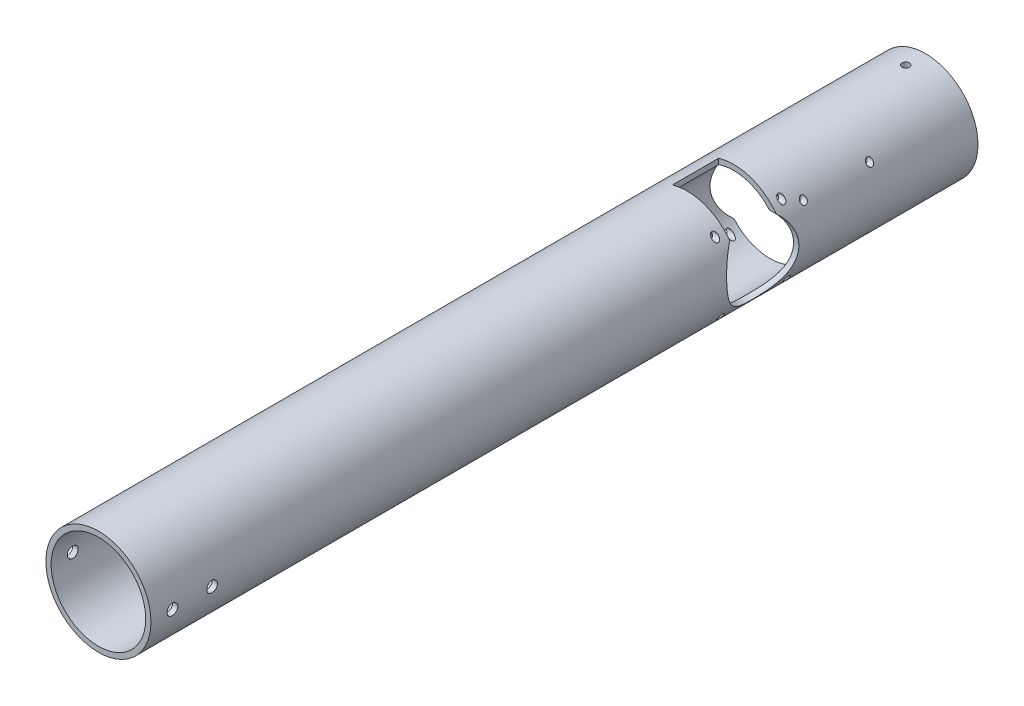
SolidWorks part; units mm, degrees
ref_plane "Front Plane" through (0, 0, 0) normal (0, 0, 1) x (1, 0, 0)
ref_plane "Top Plane" through (0, 0, 0) normal (0, 1, 0) x (1, 0, 0)
ref_plane "Right Plane" through (0, 0, 0) normal (1, 0, 0) x (0, 0, -1)
sketch "Sketch1" plane through (0, 0, 0) normal (0, 0, 1) x (1, 0, 0)
  circle A0 centre (0, 0) radius 31.75
  circle A1 centre (0, 0) radius 28.575
  dimension "D1" = 63.5
  dimension "D2" = 57.15
extrude "Boss-Extrude1" add sketch "Sketch1" along normal blind 250 and the other way blind 250 contours A1 | A0 region at (0, 0, 0)
sketch "Sketch2" plane through (0, 0, 0) normal (1, 0, 0) x (0, 0, -1)
  circle A2 centre (170, -2) radius 21.75
  dimension "D1" = 43.5
  dimension "D2" = 170
  dimension "D3" = 2
extrude "Cut-Extrude1" cut sketch "Sketch2" against normal through all
sketch "Sketch3" plane through (0, 0, 0) normal (1, 0, 0) x (0, 0, -1)
  circle A1 centre (120, 2) radius 21.75
  dimension "D1" = 120
  dimension "D2" = 43.5
  dimension "D3" = 2
extrude "Cut-Extrude2" cut sketch "Sketch3" along normal through all
sketch "Sketch5" plane through (0, 0, 0) normal (1, 0, 0) x (0, 0, -1)
  line L1 (184, -12.75) -> (156, -12.75)
  line L2 (184, -12.75) -> (184, -34.75)
  line L3 (184, -34.75) -> (156, -34.75)
  line L4 (156, -12.75) -> (156, -34.75)
  line L5 (184, -12.75) -> (156, -34.75) construction
  line L6 (184, -34.75) -> (156, -12.75) construction
  circle A0 centre (170, -2) radius 21.75 construction
  circle A1 centre (170, -2) radius 21.75 construction
  point P0 (170, -23.75)
  dimension "D1" = 28
  dimension "D2" = 22
  dimension "D3" = 170
extrude "Cut-Extrude4" cut sketch "Sketch5" against normal through all from offset 9
sketch "Sketch6" plane through (0, 0, 0) normal (1, 0, 0) x (0, 0, -1)
  line L1 (106, 34.75) -> (134, 34.75)
  line L2 (106, 34.75) -> (106, 12.75)
  line L3 (106, 12.75) -> (134, 12.75)
  line L4 (134, 34.75) -> (134, 12.75)
  line L5 (106, 34.75) -> (134, 12.75) construction
  line L6 (106, 12.75) -> (134, 34.75) construction
  circle A0 centre (120, 2) radius 21.75 construction
  circle A1 centre (120, 2) radius 21.75 construction
  point P0 (120, 23.75)
  dimension "D1" = 28
  dimension "D2" = 22
  dimension "D3" = 120
extrude "Cut-Extrude5" cut sketch "Sketch6" along normal through all from offset 9 offset against normal yes
sketch "Sketch10" plane through (0, 0, 0) normal (1, 0, 0) x (0, 0, -1)
  line L1 (210, 38) -> (130, 38)
  line L2 (210, 38) -> (210, -42)
  line L3 (210, -42) -> (130, -42)
  line L4 (130, 38) -> (130, -42)
  line L5 (210, 38) -> (130, -42) construction
  line L6 (210, -42) -> (130, 38) construction
  point P0 (170, -2)
  dimension "D1" = 80
  dimension "D2" = 80
sketch "Sketch11" plane through (0, 0, 0) normal (1, 0, 0) x (0, 0, -1)
  line L0 (210, 38) -> (130, -42) construction
  line L1 (210, -42) -> (130, 38) construction
  circle A0 centre (190, 18) radius 2
  circle A1 centre (150, 18) radius 2
  circle A2 centre (150, -22) radius 2
  circle A3 centre (190, -22) radius 2
  dimension "D5" = 4
  dimension "D6" = 4
  dimension "D7" = 4
  dimension "D8" = 4
  dimension "D1" = 20
  dimension "D2" = 20
  dimension "D3" = 20
  dimension "D4" = 20
extrude "Cut-Extrude8" cut sketch "Sketch11" against normal through all both and the other way through all
sketch "Sketch12" plane through (0, 0, 0) normal (1, 0, 0) x (0, 0, -1)
  line L1 (-250, 31.75) -> (-250, -31.75) construction
  circle A0 centre (-213, 0) radius 3.25
  circle A1 centre (-237, 0) radius 3.25
  dimension "D1" = 6.5
  dimension "D2" = 6.5
  dimension "D3" = 24
  dimension "D4" = 13
extrude "Cut-Extrude10" cut sketch "Sketch12" against normal through all both and the other way through all
sketch "Sketch13" plane through (0, 0, 0) normal (0, 1, 0) x (1, 0, 0)
  line L0 (0, -44) -> (0, 44) construction
  line L1 (28.575, 250) -> (-28.575, 250) construction
  circle A0 centre (0, 238) radius 2.25
  dimension "D2" = 4.5
  dimension "D1" = 12
extrude "Cut-Extrude11" cut sketch "Sketch13" against normal through all both and the other way through all
sketch "Sketch14" plane through (0, 0, 0) normal (1, 0, 0) x (0, 0, -1)
  line L1 (95, 27) -> (145, 27)
  line L2 (95, 27) -> (95, -23)
  line L3 (95, -23) -> (145, -23)
  line L4 (145, 27) -> (145, -23)
  line L5 (95, 27) -> (145, -23) construction
  line L6 (95, -23) -> (145, 27) construction
  circle A0 centre (100, 22) radius 2
  circle A1 centre (140, 22) radius 2
  circle A2 centre (140, -18) radius 2
  circle A3 centre (100, -18) radius 2
  point P0 (120, 2)
  dimension "D4" = 4
  dimension "D5" = 4
  dimension "D6" = 4
  dimension "D7" = 4
  dimension "D1" = 50
  dimension "D2" = 50
  dimension "D3" = 20
  dimension "D8" = 20
  dimension "D9" = 20
  dimension "D10" = 20
sketch "Sketch15" plane through (0, 0, 0) normal (1, 0, 0) x (0, 0, -1)
  circle A0 centre (100, 22) radius 2
  circle A1 centre (140, 22) radius 2
  circle A2 centre (140, -18) radius 2
  circle A3 centre (100, -18) radius 2
extrude "Cut-Extrude12" cut sketch "Sketch15" against normal through all and the other way through all
